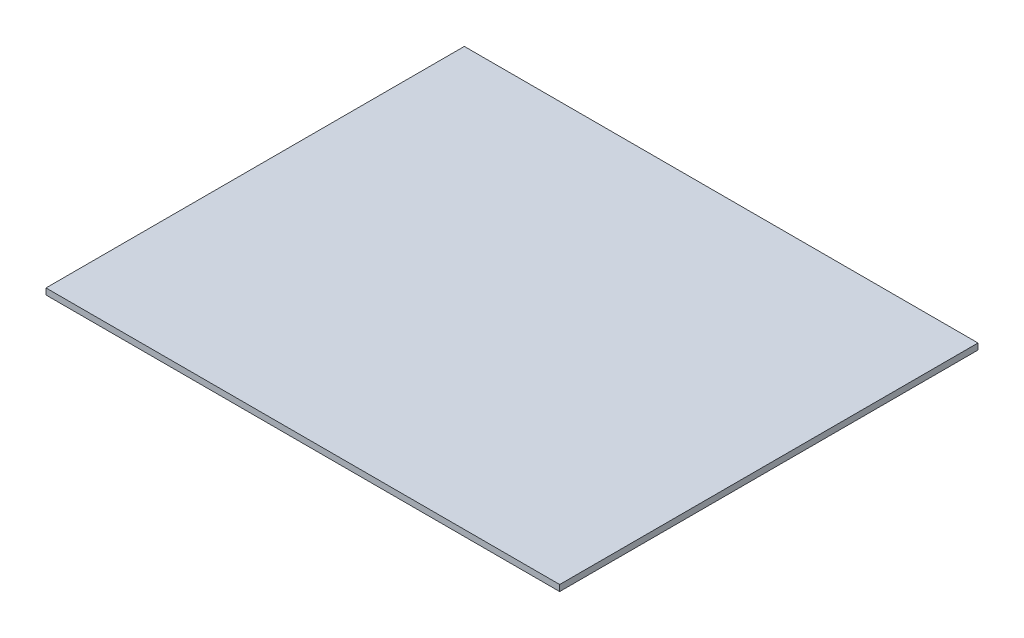
SolidWorks part; units mm, degrees
ref_plane "Front Plane" through (0, 0, 0) normal (0, 0, 1) x (1, 0, 0)
ref_plane "Top Plane" through (0, 0, 0) normal (0, 1, 0) x (1, 0, 0)
ref_plane "Right Plane" through (0, 0, 0) normal (1, 0, 0) x (0, 0, -1)
sketch "Sketch1" plane through (0, 0, 0) normal (0, 1, 0) x (1, 0, 0)
  line L0 (-62.5, -47) -> (-62.5, 47)
  line L1 (-60.5, -45) -> (60.5, -45)
  line L2 (-60.5, -45) -> (-60.5, 7)
  line L4 (60.5, -45) -> (60.5, 7)
  line L5 (-62.5, 47) -> (62.5, 47)
  line L6 (62.5, -47) -> (62.5, 47)
  line L7 (-62.5, -47) -> (62.5, -47)
  line L8 (-60.5, 7) -> (60.5, 7)
  line L9 (0, 0) -> (0, 7) construction
  line L10 (-60.5, -45) -> (-60.5, 45) construction
  line L11 (-60.5, 45) -> (60.5, 45) construction
  line L12 (60.5, -45) -> (60.5, 45) construction
  line L13 (-83.5, -68) -> (-83.5, 68)
  line L14 (-83.5, 68) -> (83.5, 68)
  line L15 (83.5, -68) -> (83.5, 68)
  line L16 (-83.5, -68) -> (83.5, -68)
  point P0 (0, 0)
  point P6 (0, -47)
  point P7 (62.5, 0)
  point P14 (0, 7)
  dimension "D1" = 94
  dimension "D2" = 125
  dimension "D4" = 40
  dimension "D3" = 2
  dimension "D5" = 21
extrude "Main" add sketch "Sketch1" along normal blind 10 contours L0 L7 L6 L5 L4 L1 L2 region at (0, 0, -21.9033)
ref_plane "BacklitPlane" through (0, 10, 0) normal (0, 1, 0) x (1, 0, 0)
extrude "Boss-Extrude3" add sketch "Sketch1<4>" along normal blind 2 from surface contours L13 L16 L15 L14 L7 L0 L5 L6 | L8 L2 L1 L4 | L0 L7 L6 L5 L2 L8 L4 L1 region at (0, 0, -21.9033) region at (0, 0, 19) region at (-81.3463, 0, 0) starting at plane "BacklitPlane"
sketch "Sketch1<4>" plane through (0, 0, 0) normal (0, 1, 0) x (1, 0, 0) same geometry as "Sketch1"
sketch "Sketch5" plane through (0, 0, 0) normal (0, -1, 0) x (1, 0, 0)
  circle A0 centre (-50, -35) radius 3.5
  dimension "D3" = 7
  dimension "D1" = 50
  dimension "D2" = 35
extrude "Boss-Extrude4" add sketch "Sketch5" along normal blind 4.2
sketch3d "3DSketch2"
  line L0 (-50, -4.2, -35) -> (-50, 0, -35) construction
  point P0 (-50, -4.2, -35)
ref_plane "Plane2" through (0, 0, -35) normal (0, 0, 1) x (1, 0, 0)
sketch "Sketch8" plane through (0, 0, -35) normal (0, 0, 1) x (1, 0, 0)
  line L0 (-50, -8.4) -> (-50, 0) construction
  line L1 (-53.5, 0) -> (-46.5, 0) construction
  line L2 (-43, -4.2) -> (-57, -4.2)
  arc A1 (-57, -4.2) -> (-43, -4.2) centre (-50, 2.9414) ccw
  point P7 (-50, -4.2)
  point P12 (-50, -4.2)
  dimension "D2" = 10
  dimension "D1" = 14
revolve "Revolve1" add sketch "Sketch8" angle 360 about L0 region at (-50, -5.3587, -35)
mirror "Mirror1" about plane through (0, 0, 0) normal (1, 0, 0) of "Revolve1", "Boss-Extrude4"
sketch "Sketch11" plane through (0, 0, 0) normal (0, -1, 0) x (1, 0, 0)
  line L0 (-62.5, 47) -> (-62.5, -47) construction
  line L1 (-60.5, 45) -> (-62.5, 45)
  line L2 (-60.5, 45) -> (-60.5, 39)
  line L3 (-60.5, 39) -> (-62.5, 39)
  line L4 (-62.5, 45) -> (-62.5, 39)
  line L5 (62.5, 47) -> (62.5, -47) construction
  line L6 (60.5, 45) -> (62.5, 45)
  line L7 (60.5, 45) -> (60.5, 39)
  line L8 (60.5, 39) -> (62.5, 39)
  line L9 (62.5, 45) -> (62.5, 39)
  line L10 (-60.5, 45) -> (60.5, 45) construction
  line L11 (-3, 45) -> (3, 45)
  line L12 (-3, 45) -> (-3, 47)
  line L13 (-3, 47) -> (3, 47)
  line L14 (3, 45) -> (3, 47)
  line L15 (-62.5, 47) -> (62.5, 47) construction
  point P22 (0, 45)
  point P23 (0, 45)
  dimension "D1" = 6
  dimension "D2" = 6
  dimension "D3" = 6
extrude "Cut-Extrude1" cut sketch "Sketch11" against normal up to surface (10 mm away) up to face at (0, 10, 0)
